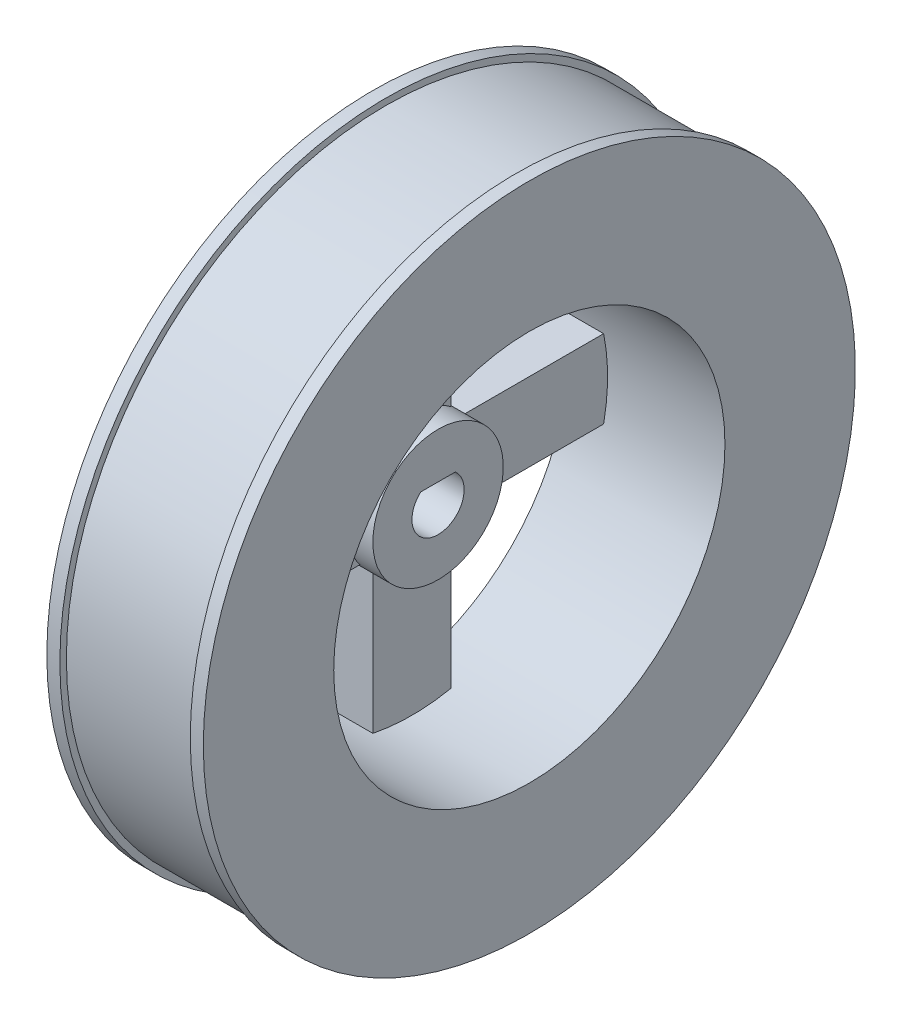
SolidWorks part; units mm, degrees
material "PLA (Black)"
ref_plane "Front Plane" through (0, 0, 0) normal (0, 0, 1) x (1, 0, 0)
ref_plane "Top Plane" through (0, 0, 0) normal (0, 1, 0) x (1, 0, 0)
ref_plane "Right Plane" through (0, 0, 0) normal (1, 0, 0) x (0, 0, -1)
sketch "Sketch1" plane through (0, 0, 0) normal (0, 0, 1) x (1, 0, 0)
  line L0 (0, 0) -> (41532.2986, 0) construction
  line L1 (-6, 25) -> (-6, 15)
  line L3 (6, 15) -> (6, 25)
  line L4 (6, 25) -> (5, 25)
  line L5 (5, 25) -> (5, 24.5)
  line L6 (5, 24.5) -> (-5, 24.5)
  line L7 (-5, 24.5) -> (-5, 25)
  line L8 (-5, 25) -> (-6, 25)
  line L9 (-6, 15) -> (6, 15)
  line L10 (-1, 5) -> (-6, 5)
  line L11 (-6, 5) -> (-6, 0)
  line L12 (-6, 0) -> (-1, 0)
  line L13 (-1, 0) -> (-1, 5)
  point P15 (0, 15)
  dimension "D1" = 50
  dimension "D2" = 0.5
  dimension "D3" = 1
  dimension "D4" = 10
  dimension "D5" = 10
  dimension "D6" = 10
  dimension "D7" = 5
revolve "Revolve1" add sketch "Sketch1" angle 360 about L0
sketch "Sketch2" plane through (-6, 0, 0) normal (1, 0, 0) x (0, 0, -1)
  line L2 (0, 0) -> (0, 50000) construction
  line L9 (-3, 4) -> (-3, 14.6969)
  line L10 (3, 4) -> (3, 14.6969)
  arc A0 (-3, 14.6969) -> (3, 14.6969) centre (0, 0) cw
  circle A12 centre (0, 0) radius 15 construction
  circle A13 centre (0, 0) radius 5
  arc A14 (3, 4) -> (-3, 4) centre (0, 0) ccw
  dimension "D2" = 6
  dimension "D3" = 0
extrude "Boss-Extrude1" add sketch "Sketch2" along normal blind 3
sketch "Sketch3" plane through (-1, 0, 0) normal (1, 0, 0) x (0, 0, -1)
  line L0 (-1.3229, 1.5) -> (1.3229, 1.5)
  arc A0 (-1.3229, 1.5) -> (1.3229, 1.5) centre (0, 0) ccw
  dimension "D1" = 4
  dimension "D2" = 1.5
extrude "Cut-Extrude1" cut sketch "Sketch3" against normal through all both and the other way through all
pattern_circular "CirPattern1" count 4 over 360 about axis through (-6, 0, 0) along (1, 0, 0) of "Boss-Extrude1" reverse direction yes
